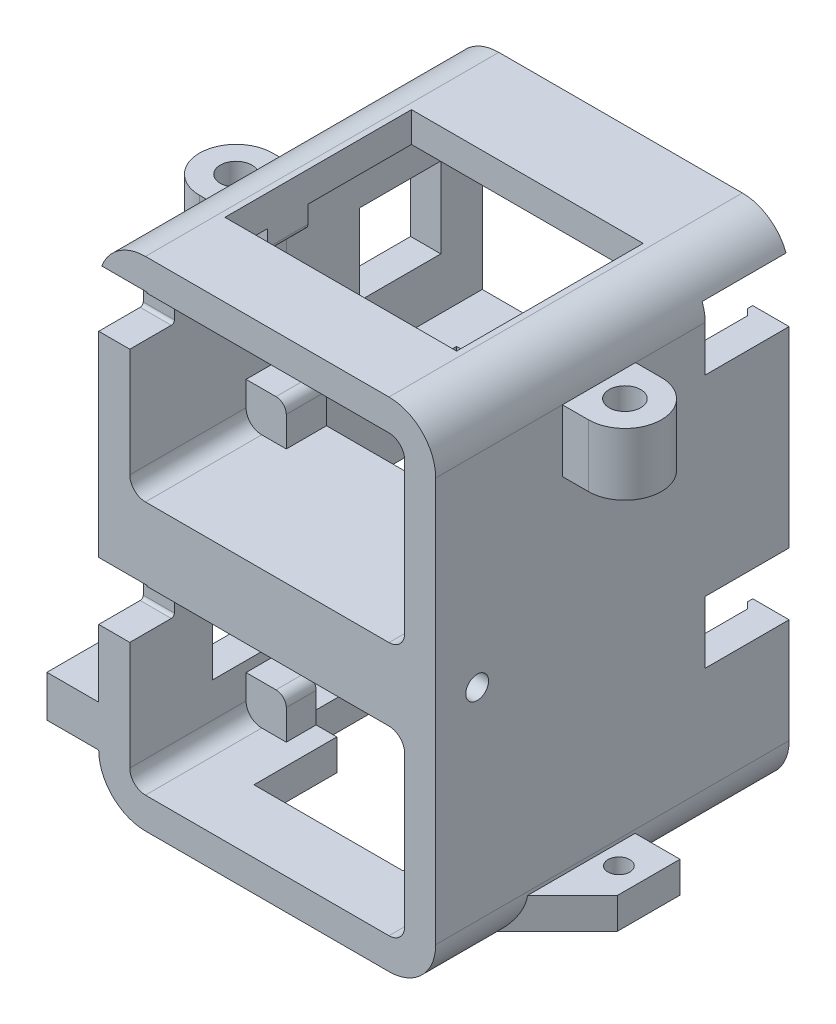
SolidWorks part; units mm, degrees
ref_plane "前视基准面" through (0, 0, 0) normal (0, 0, 1) x (1, 0, 0)
ref_plane "上视基准面" through (0, 0, 0) normal (0, 1, 0) x (1, 0, 0)
ref_plane "右视基准面" through (0, 0, 0) normal (1, 0, 0) x (0, 0, -1)
other "Configuration Table"
sketch "草图2" plane through (0, 0, 0) normal (0, 0, 1) x (1, 0, 0)
  line L20 (13.26, -7.25) -> (13.26, 7.25)
  line L21 (11.75, 8.76) -> (-16.76, 8.76)
  line L22 (-16.76, 8.76) -> (-16.76, 3.34)
  line L23 (-16.76, 3.34) -> (-13.26, 3.34)
  line L24 (-13.26, 3.34) -> (-13.26, -7.25)
  line L25 (-11.75, -8.76) -> (-3.99, -8.76)
  line L26 (-3.99, -8.76) -> (-3.99, -7.76)
  line L27 (-3.99, -7.76) -> (3.99, -7.76)
  line L28 (3.99, -7.76) -> (3.99, -8.76)
  line L29 (3.99, -8.76) -> (11.75, -8.76)
  line L40 (13.26, -7.25) -> (13.26, 7.25)
  line L41 (11.75, 8.76) -> (-16.76, 8.76)
  line L42 (-16.76, 8.76) -> (-16.76, 3.34)
  line L43 (-16.76, 3.34) -> (-13.26, 3.34)
  line L44 (-13.26, 3.34) -> (-13.26, -7.25)
  line L45 (-11.75, -8.76) -> (-3.99, -8.76)
  line L49 (3.99, -8.76) -> (11.75, -8.76)
  line L50 (-3.99, 15.74) -> (3.99, 15.74)
  line L51 (-3.99, -8.76) -> (3.99, -8.76)
  line L52 (-3.99, 12.74) -> (3.99, 12.74)
  line L53 (3.99, 12.74) -> (11.75, 12.74)
  line L54 (16.26, 17.25) -> (16.26, 31.75)
  line L55 (11.75, 36.26) -> (-19.76, 36.26)
  line L56 (-19.76, 36.26) -> (-19.76, 24.84)
  line L57 (-19.76, 24.84) -> (-16.26, 24.84)
  line L58 (-16.26, 24.84) -> (-16.26, 17.25)
  line L59 (-11.75, 12.74) -> (-3.99, 12.74)
  line L70 (13.26, 17.25) -> (13.26, 31.75)
  line L71 (11.75, 33.26) -> (-16.76, 33.26)
  line L72 (-16.76, 33.26) -> (-16.76, 27.84)
  line L73 (-16.76, 27.84) -> (-13.26, 27.84)
  line L74 (-13.26, 27.84) -> (-13.26, 17.25)
  line L75 (-11.75, 15.74) -> (-3.99, 15.74)
  line L76 (-3.99, 15.74) -> (-3.99, 16.74)
  line L77 (-3.99, 16.74) -> (3.99, 16.74)
  line L78 (3.99, 16.74) -> (3.99, 15.74)
  line L79 (3.99, 15.74) -> (11.75, 15.74)
  line L80 (13.26, 17.25) -> (13.26, 31.75)
  line L81 (11.75, 33.26) -> (-16.76, 33.26)
  line L82 (-16.76, 33.26) -> (-16.76, 27.84)
  line L83 (-16.76, 27.84) -> (-13.26, 27.84)
  line L84 (-13.26, 27.84) -> (-13.26, 17.25)
  line L85 (-11.75, 15.74) -> (-3.99, 15.74)
  line L89 (3.99, 15.74) -> (11.75, 15.74)
  line L90 (16.26, -7.25) -> (16.26, 7.25)
  line L91 (11.75, 11.76) -> (-19.76, 11.76)
  line L92 (-19.76, 11.76) -> (-19.76, 0.34)
  line L93 (-19.76, 0.34) -> (-16.26, 0.34)
  line L94 (-16.26, 0.34) -> (-16.26, -7.25)
  line L95 (-11.75, -11.76) -> (-3.99, -11.76)
  line L96 (-3.99, -11.76) -> (3.99, -11.76)
  line L97 (3.99, -11.76) -> (11.75, -11.76)
  line L98 (-16.26, 0.34) -> (-16.26, 3.34)
  line L99 (-16.26, 17.25) -> (-16.26, 11.76)
  line L100 (16.26, 17.25) -> (16.26, 7.25)
  line L101 (-16.76, 33.26) -> (-19.76, 33.26)
  line L102 (-16.76, 27.84) -> (-19.76, 27.84)
  line L103 (-16.76, 8.76) -> (-19.76, 8.76)
  line L104 (-16.26, 24.84) -> (-16.26, 27.84)
  line L105 (-16.26, 36.26) -> (-16.26, 33.26)
  line L106 (-16.26, 11.76) -> (-16.26, 8.76)
  line L107 (-16.26, 33.26) -> (-16.26, 27.84)
  line L108 (-16.26, 8.76) -> (-16.26, 3.34)
  line L109 (-13.26, 27.84) -> (-13.26, 33.26)
  line L110 (-13.26, 3.34) -> (-13.26, 8.76)
  arc A1 (-11.75, 11.76) -> (-16.26, 7.25) centre (-11.75, 7.25) ccw
  arc A2 (-11.75, 8.76) -> (-13.26, 7.25) centre (-11.75, 7.25) ccw
  arc A3 (-11.75, 8.76) -> (-13.26, 7.25) centre (-11.75, 7.25) ccw
  arc A6 (13.26, 7.25) -> (11.75, 8.76) centre (11.75, 7.25) ccw
  arc A7 (-13.26, -7.25) -> (-11.75, -8.76) centre (-11.75, -7.25) ccw
  arc A8 (11.75, -8.76) -> (13.26, -7.25) centre (11.75, -7.25) ccw
  arc A12 (13.26, 7.25) -> (11.75, 8.76) centre (11.75, 7.25) ccw
  arc A13 (-13.26, -7.25) -> (-11.75, -8.76) centre (-11.75, -7.25) ccw
  arc A14 (11.75, -8.76) -> (13.26, -7.25) centre (11.75, -7.25) ccw
  arc A15 (11.75, 12.74) -> (16.26, 17.25) centre (11.75, 17.25) ccw
  arc A16 (16.26, 31.75) -> (11.75, 36.26) centre (11.75, 31.75) ccw
  arc A17 (-16.26, 17.25) -> (-11.75, 12.74) centre (-11.75, 17.25) ccw
  arc A21 (13.26, 31.75) -> (11.75, 33.26) centre (11.75, 31.75) ccw
  arc A22 (-13.26, 17.25) -> (-11.75, 15.74) centre (-11.75, 17.25) ccw
  arc A23 (11.75, 15.74) -> (13.26, 17.25) centre (11.75, 17.25) ccw
  arc A24 (13.26, 31.75) -> (11.75, 33.26) centre (11.75, 31.75) ccw
  arc A25 (-13.26, 17.25) -> (-11.75, 15.74) centre (-11.75, 17.25) ccw
  arc A26 (11.75, 15.74) -> (13.26, 17.25) centre (11.75, 17.25) ccw
  arc A27 (16.26, 7.25) -> (11.75, 11.76) centre (11.75, 7.25) ccw
  arc A28 (-16.26, -7.25) -> (-11.75, -11.76) centre (-11.75, -7.25) ccw
  arc A29 (11.75, -11.76) -> (16.26, -7.25) centre (11.75, -7.25) ccw
  arc A31 (-11.75, 36.26) -> (-16.26, 31.75) centre (-11.75, 31.75) ccw
  arc A32 (-11.75, 33.26) -> (-13.26, 31.75) centre (-11.75, 31.75) ccw
  arc A33 (-11.75, 33.26) -> (-13.26, 31.75) centre (-11.75, 31.75) ccw
  dimension "D4" = 3
  dimension "D6" = 3
  dimension "D7" = 0.01
  dimension "D8" = 3
extrude "凸台-拉伸2" add sketch "草图2" against normal up to surface (11.22 mm away)
sketch "草图3" plane through (0, 0, -11.22) normal (0, 0, -1) x (-1, 0, 0)
  line L0 (11.75, -8.76) -> (-11.75, -8.76) construction
  line L2 (-11.75, 8.76) -> (11.75, 8.76) construction
  line L3 (11.75, -8.76) -> (-11.75, -8.76)
  line L4 (16.26, -7.25) -> (16.26, 31.75)
  line L5 (11.75, 36.26) -> (-11.75, 36.26)
  line L6 (-16.26, 31.75) -> (-16.26, -7.25)
  line L7 (-11.75, -11.76) -> (11.75, -11.76)
  line L12 (16.26, -7.25) -> (16.26, 31.75)
  line L13 (11.75, 36.26) -> (-11.75, 36.26)
  line L14 (-16.26, 31.75) -> (-16.26, -7.25)
  line L16 (-11.75, -11.76) -> (11.75, -11.76)
  line L20 (-13.26, -7.25) -> (-13.26, 7.25)
  line L21 (-11.75, 33.26) -> (11.75, 33.26) construction
  line L22 (-13.26, 17.25) -> (-13.26, 31.75) construction
  line L23 (-9.38, -8.74) -> (-9.38, -5.87)
  line L24 (-10.37, -4.88) -> (-13.24, -4.88)
  line L25 (-13.24, -4.88) -> (-13.24, -7.25)
  line L26 (-11.75, -8.74) -> (-9.38, -8.74)
  line L27 (-9.38, -8.74) -> (-9.38, -5.87)
  line L28 (-10.37, -4.88) -> (-13.24, -4.88)
  line L32 (11.75, 15.74) -> (-11.75, 15.74) construction
  line L33 (-11.75, 33.26) -> (11.75, 33.26)
  line L34 (-13.26, 17.25) -> (-13.26, 31.75)
  line L36 (11.75, 15.74) -> (-11.75, 15.74)
  line L38 (13.26, 7.25) -> (13.26, -7.25) construction
  line L39 (13.24, -4.88) -> (10.37, -4.88)
  line L40 (9.38, -5.87) -> (9.38, -8.74)
  line L41 (9.38, -8.74) -> (11.75, -8.74)
  line L42 (13.24, -7.25) -> (13.24, -4.88)
  line L43 (13.24, -4.88) -> (10.37, -4.88)
  line L44 (9.38, -5.87) -> (9.38, -8.74)
  line L47 (13.26, 7.25) -> (13.26, -7.25)
  line L48 (-11.75, 8.76) -> (11.75, 8.76) construction
  line L49 (-9.38, 15.75) -> (-9.38, 18.63)
  line L50 (-10.37, 19.62) -> (-13.25, 19.62)
  line L51 (-13.24, 6.68) -> (-11.67, 6.68)
  line L52 (-11.18, 7.17) -> (-11.18, 8.74)
  line L53 (-11.18, 8.74) -> (-11.75, 8.74)
  line L54 (-13.24, 7.25) -> (-13.24, 6.68)
  line L55 (-13.24, 6.68) -> (-11.67, 6.68)
  line L56 (-11.18, 7.17) -> (-11.18, 8.74)
  line L59 (-13.24, 6.68) -> (-13.26, 6.68)
  line L60 (-13.26, -7.25) -> (-13.26, 7.25) construction
  line L61 (-9.38, 15.74) -> (-9.38, 18.63)
  line L62 (-10.37, 19.62) -> (-13.26, 19.62)
  line L63 (11.18, 8.74) -> (11.18, 7.17)
  line L64 (11.67, 6.68) -> (13.24, 6.68)
  line L65 (13.24, 6.68) -> (13.24, 7.25)
  line L66 (11.75, 8.74) -> (11.18, 8.74)
  line L67 (11.18, 8.76) -> (11.18, 7.17)
  line L68 (11.67, 6.68) -> (13.26, 6.68)
  line L71 (-11.75, 8.76) -> (11.75, 8.76)
  line L73 (-13.25, 31.18) -> (-11.67, 31.18)
  line L74 (-11.18, 31.67) -> (-11.18, 33.25)
  line L75 (-13.25, 31.18) -> (-11.67, 31.18)
  line L76 (-11.18, 31.67) -> (-11.18, 33.25)
  line L79 (11.67, 31.18) -> (13.25, 31.18)
  line L80 (11.18, 33.25) -> (11.18, 31.67)
  line L81 (11.67, 31.18) -> (13.26, 31.18)
  line L82 (11.18, 33.25) -> (11.18, 31.67)
  line L83 (-13.25, 31.18) -> (-13.26, 31.18)
  line L84 (-11.18, 33.25) -> (-11.18, 33.26)
  line L85 (9.38, 18.63) -> (9.38, 15.75)
  line L86 (13.25, 19.62) -> (10.37, 19.62)
  line L87 (9.38, 18.63) -> (9.38, 15.74)
  line L88 (13.26, 19.62) -> (10.37, 19.62)
  line L89 (11.18, 33.25) -> (11.18, 33.26)
  line L90 (-11.18, 8.74) -> (-11.18, 8.76)
  line L91 (13.26, 31.75) -> (13.26, 17.25) construction
  line L92 (13.26, 31.75) -> (13.26, 17.25)
  line L93 (-13.24, -4.88) -> (-13.26, -4.88)
  line L94 (-9.38, -8.74) -> (-9.38, -8.76)
  line L95 (9.38, -8.74) -> (9.38, -8.76)
  line L96 (13.24, -4.88) -> (13.26, -4.88)
  arc A0 (-13.26, -7.25) -> (-11.75, -8.76) centre (-11.75, -7.25) ccw construction
  arc A1 (11.75, -8.76) -> (13.26, -7.25) centre (11.75, -7.25) ccw construction
  arc A2 (-11.75, 8.76) -> (-13.26, 7.25) centre (-11.75, 7.25) ccw construction
  arc A3 (11.75, -11.76) -> (16.26, -7.25) centre (11.75, -7.25) ccw
  arc A4 (-11.75, 36.26) -> (-16.26, 31.75) centre (-11.75, 31.75) ccw
  arc A5 (-16.26, -7.25) -> (-11.75, -11.76) centre (-11.75, -7.25) ccw
  arc A6 (11.75, -11.76) -> (16.26, -7.25) centre (11.75, -7.25) ccw
  arc A9 (-11.75, 36.26) -> (-16.26, 31.75) centre (-11.75, 31.75) ccw
  arc A10 (-9.38, -5.87) -> (-10.37, -4.88) centre (-10.37, -5.87) ccw
  arc A11 (-13.24, -7.25) -> (-11.75, -8.74) centre (-11.75, -7.25) ccw
  arc A12 (-9.38, -5.87) -> (-10.37, -4.88) centre (-10.37, -5.87) ccw
  arc A14 (-16.26, -7.25) -> (-11.75, -11.76) centre (-11.75, -7.25) ccw
  arc A15 (-13.26, -7.25) -> (-11.75, -8.76) centre (-11.75, -7.25) ccw
  arc A16 (11.75, -8.76) -> (13.26, -7.25) centre (11.75, -7.25) ccw
  arc A17 (-11.75, 8.76) -> (-13.26, 7.25) centre (-11.75, 7.25) ccw
  arc A18 (10.37, -4.88) -> (9.38, -5.87) centre (10.37, -5.87) ccw
  arc A19 (11.75, -8.74) -> (13.24, -7.25) centre (11.75, -7.25) ccw
  arc A20 (10.37, -4.88) -> (9.38, -5.87) centre (10.37, -5.87) ccw
  arc A22 (-11.75, 33.26) -> (-13.26, 31.75) centre (-11.75, 31.75) ccw construction
  arc A23 (11.75, 15.74) -> (13.26, 17.25) centre (11.75, 17.25) ccw construction
  arc A24 (-11.67, 6.68) -> (-11.18, 7.17) centre (-11.67, 7.17) ccw
  arc A25 (-11.75, 8.74) -> (-13.24, 7.25) centre (-11.75, 7.25) ccw
  arc A26 (-11.67, 6.68) -> (-11.18, 7.17) centre (-11.67, 7.17) ccw
  arc A28 (-13.26, 17.25) -> (-11.75, 15.74) centre (-11.75, 17.25) ccw construction
  arc A29 (-11.75, 33.26) -> (-13.26, 31.75) centre (-11.75, 31.75) ccw
  arc A30 (11.18, 7.17) -> (11.67, 6.68) centre (11.67, 7.17) ccw
  arc A31 (13.24, 7.25) -> (11.75, 8.74) centre (11.75, 7.25) ccw
  arc A32 (11.18, 7.17) -> (11.67, 6.68) centre (11.67, 7.17) ccw
  arc A34 (11.75, 15.74) -> (13.26, 17.25) centre (11.75, 17.25) ccw
  arc A35 (-13.26, 17.25) -> (-11.75, 15.74) centre (-11.75, 17.25) ccw
  arc A36 (13.26, 7.25) -> (11.75, 8.76) centre (11.75, 7.25) ccw construction
  arc A37 (13.26, 7.25) -> (11.75, 8.76) centre (11.75, 7.25) ccw
  arc A38 (-9.38, 18.63) -> (-10.37, 19.62) centre (-10.37, 18.63) ccw
  arc A39 (-9.38, 18.63) -> (-10.37, 19.62) centre (-10.37, 18.63) ccw
  arc A41 (-11.67, 31.18) -> (-11.18, 31.67) centre (-11.67, 31.67) ccw
  arc A42 (-11.67, 31.18) -> (-11.18, 31.67) centre (-11.67, 31.67) ccw
  arc A44 (11.18, 31.67) -> (11.67, 31.18) centre (11.67, 31.67) ccw
  arc A45 (11.18, 31.67) -> (11.67, 31.18) centre (11.67, 31.67) ccw
  arc A46 (13.26, 31.75) -> (11.75, 33.26) centre (11.75, 31.75) ccw construction
  arc A47 (10.37, 19.62) -> (9.38, 18.63) centre (10.37, 18.63) ccw
  arc A48 (10.37, 19.62) -> (9.38, 18.63) centre (10.37, 18.63) ccw
  arc A49 (13.26, 31.75) -> (11.75, 33.26) centre (11.75, 31.75) ccw
  arc A52 (16.26, 31.75) -> (11.75, 36.26) centre (11.75, 31.75) ccw
  arc A53 (16.26, 31.75) -> (11.75, 36.26) centre (11.75, 31.75) ccw
  dimension "D7" = 0.01
  dimension "D9" = 0.01
extrude "凸台-拉伸3" add sketch "草图3" along normal up to surface (3.88 mm away)
sketch "草图4" plane through (-16.26, 0, 0) normal (-1, 0, 0) x (0, 0, 1)
  line L8 (0.1, 8.85) -> (-4, 8.85)
  line L9 (-4.3, 8.55) -> (-4.3, 3.55)
  line L10 (-4, 3.25) -> (0.1, 3.25)
  line L11 (0.1, 3.25) -> (0.1, 8.85)
  line L12 (0.1, 8.85) -> (-4, 8.85)
  line L13 (-4.3, 8.55) -> (-4.3, 3.55)
  line L14 (-4, 3.25) -> (0.1, 3.25)
  line L15 (0.1, 3.25) -> (0.1, 8.85)
  line L20 (0.1, 33.35) -> (-4, 33.35)
  line L21 (-4.3, 33.05) -> (-4.3, 28.05)
  line L22 (-4, 27.75) -> (0.1, 27.75)
  line L23 (0.1, 27.75) -> (0.1, 33.35)
  line L24 (0.1, 33.35) -> (-4, 33.35)
  line L25 (-4.3, 33.05) -> (-4.3, 28.05)
  line L26 (-4, 27.75) -> (0.1, 27.75)
  line L27 (0.1, 27.75) -> (0.1, 33.35)
  arc A4 (-4, 8.85) -> (-4.3, 8.55) centre (-4, 8.55) ccw
  arc A5 (-4.3, 3.55) -> (-4, 3.25) centre (-4, 3.55) ccw
  arc A6 (-4, 8.85) -> (-4.3, 8.55) centre (-4, 8.55) ccw
  arc A7 (-4.3, 3.55) -> (-4, 3.25) centre (-4, 3.55) ccw
  arc A10 (-4, 33.35) -> (-4.3, 33.05) centre (-4, 33.05) ccw
  arc A11 (-4.3, 28.05) -> (-4, 27.75) centre (-4, 28.05) ccw
  arc A12 (-4, 33.35) -> (-4.3, 33.05) centre (-4, 33.05) ccw
  arc A13 (-4.3, 28.05) -> (-4, 27.75) centre (-4, 28.05) ccw
extrude "切除-拉伸1" cut sketch "草图4" against normal blind 4.65
ref_plane "基准面1" through (0, 31.75, 0) normal (0, 1, 0) x (1, 0, 0)
sketch "草图8" plane through (0, 31.75, 0) normal (0, 1, 0) x (1, 0, 0)
  line L0 (18.76, 12.23) -> (15.235, 12.23)
  line L1 (15.235, 12.23) -> (15.235, 15.755)
  line L2 (16.26, 15.1) -> (16.26, 0) construction
  line L3 (-12.113, 15.755) -> (15.235, 15.755) construction
  line L4 (9.73, 15.91) -> (-9.73, 15.91) construction
  line L5 (-9.73, 15.6) -> (9.73, 15.6) construction
  line L9 (18.76, 19.28) -> (15.235, 19.28)
  line L10 (15.235, 15.755) -> (15.235, 19.28)
  circle A2 centre (18.76, 15.755) radius 1.525
  circle A3 centre (18.76, 15.755) radius 3.525
  dimension "D1" = 3.05
  dimension "D3" = 2.5
  dimension "D2" = 2
extrude "凸台-拉伸5" add sketch "草图8" against normal blind 6 contours A3 A2 | A3 L9 L10 | A3 L1 L0
mirror "镜向1" about plane through (0, 0, 0) normal (1, 0, 0) of "凸台-拉伸5"
sketch "草图9" plane through (0, 0, -15.1) normal (0, 0, -1) x (-1, 0, 0)
  line L0 (-11.18, 33.26) -> (11.18, 33.26) construction
  line L1 (-11.18, 33.26) -> (11.18, 33.26)
  line L2 (-11.18, 33.26) -> (-11.18, 36.26)
  line L3 (-11.18, 36.26) -> (11.18, 36.26)
  line L4 (11.18, 33.26) -> (11.18, 36.26)
  line L5 (11.75, 36.26) -> (-11.75, 36.26) construction
  line L6 (-11.18, 31.67) -> (-11.18, 33.26) construction
  line L7 (11.18, 33.26) -> (11.18, 31.67) construction
extrude "切除-拉伸3" cut sketch "草图9" against normal blind 8
sketch "草图10" plane through (0, 0, -15.1) normal (0, 0, -1) x (-1, 0, 0)
  line L0 (-11.75, -11.76) -> (11.75, -11.76) construction
  line L1 (-10.73, -11.76) -> (10.73, -11.76)
  line L2 (-10.73, -11.76) -> (-10.73, -4.88)
  line L3 (-10.73, -4.88) -> (10.73, -4.88)
  line L4 (10.73, -11.76) -> (10.73, -4.88)
  line L5 (13.26, -4.88) -> (10.37, -4.88) construction
  line L6 (-9.73, 21.7989) -> (-9.73, 20.8989) construction
  line L7 (9.73, 69.5489) -> (9.73, -48.1511) construction
  dimension "D1" = 1
  dimension "D2" = 1
extrude "切除-拉伸4" cut sketch "草图10" against normal blind 1
sketch "草图12" plane through (-16.26, 0, 0) normal (-1, 0, 0) x (0, 0, 1)
  line L0 (0, 8.85) -> (0, 27.75) construction
  line L1 (-11.22, 8.76) -> (-4.2142, 8.76) construction
  line L2 (-11.22, 15.74) -> (0, 15.74) construction
  line L3 (-11.22, 8.76) -> (-4.2142, 8.76)
  line L4 (-11.22, 15.74) -> (0, 15.74)
  line L5 (-8.8508, 12.25) -> (0.722, 12.25) construction
  circle A0 centre (-4, 12.25) radius 1.1
  dimension "D1" = 2.2
  dimension "D2" = 4
extrude "切除-拉伸5" cut sketch "草图12" against normal blind 8 contours A0 L5 | L5 A0
mirror "镜向2" about plane through (0, 0, 0) normal (1, 0, 0) of "切除-拉伸5"
sketch "草图14" plane through (0, 0, -15.1) normal (0, 0, -1) x (-1, 0, 0)
  line L0 (-16.26, 19.53) -> (16.26, 19.53)
  line L2 (-16.26, 8.85) -> (16.26, 8.85)
  line L3 (-10.37, 19.63) -> (-13.25, 19.63) construction
  line L13 (-11.17, 8.75) -> (11.17, 8.75) construction
  line L19 (16.26, 3.25) -> (13.26, 3.25)
  line L20 (16.26, -7.25) -> (16.26, 3.25)
  line L21 (-11.75, -11.76) -> (11.75, -11.76)
  line L22 (-16.26, 31.75) -> (-16.26, -7.25)
  line L23 (11.75, 36.26) -> (-11.75, 36.26)
  line L24 (11.61, 33.35) -> (15.9666, 33.35)
  line L26 (-11.75, 33.26) -> (11.61, 33.26)
  line L27 (-13.26, 17.25) -> (-13.26, 31.75)
  line L28 (11.75, 15.74) -> (-11.75, 15.74)
  line L29 (13.26, 27.75) -> (13.26, 17.25)
  line L30 (16.26, 27.75) -> (13.26, 27.75)
  line L31 (16.26, 8.85) -> (16.26, 27.75)
  line L32 (11.61, 8.85) -> (16.26, 8.85)
  line L34 (-11.75, 8.76) -> (11.61, 8.76)
  line L35 (-13.26, -7.25) -> (-13.26, 7.25)
  line L36 (11.75, -8.76) -> (-11.75, -8.76)
  line L37 (13.26, 3.25) -> (13.26, -7.25)
  line L39 (16.26, -7.25) -> (16.26, 8.85)
  line L40 (-11.75, -11.76) -> (11.75, -11.76)
  line L41 (-16.26, 31.75) -> (-16.26, -7.25)
  line L42 (11.75, 36.26) -> (-11.75, 36.26)
  line L50 (16.26, 8.85) -> (16.26, 31.75)
  line L66 (11.61, 33.26) -> (11.61, 33.35)
  line L67 (11.61, 8.76) -> (11.61, 8.85)
  line L1654 (-9.83, 69.5959) -> (-9.83, -48.2511)
  line L1655 (-9.83, -48.2511) -> (9.83, -48.2511)
  line L1656 (9.83, -48.2511) -> (9.83, 69.5959)
  line L1657 (-9.83, 69.5959) -> (-9.83, -48.2511)
  line L1658 (-9.83, -48.2511) -> (9.83, -48.2511)
  line L1659 (9.83, -48.2511) -> (9.83, 69.5959)
  arc A4 (9.83, 69.5959) -> (-9.83, 69.5959) centre (0, 57.7742) ccw
  arc A5 (9.83, 69.5959) -> (-9.83, 69.5959) centre (0, 57.7742) ccw
  arc A10 (11.75, -11.76) -> (16.26, -7.25) centre (11.75, -7.25) ccw
  arc A11 (-16.26, -7.25) -> (-11.75, -11.76) centre (-11.75, -7.25) ccw
  arc A12 (-11.75, 36.26) -> (-16.26, 31.75) centre (-11.75, 31.75) ccw
  arc A13 (15.9666, 33.35) -> (11.75, 36.26) centre (11.75, 31.75) ccw
  arc A14 (-11.75, 33.26) -> (-13.26, 31.75) centre (-11.75, 31.75) ccw
  arc A15 (-13.26, 17.25) -> (-11.75, 15.74) centre (-11.75, 17.25) ccw
  arc A16 (11.75, 15.74) -> (13.26, 17.25) centre (11.75, 17.25) ccw
  arc A17 (-11.75, 8.76) -> (-13.26, 7.25) centre (-11.75, 7.25) ccw
  arc A18 (-13.26, -7.25) -> (-11.75, -8.76) centre (-11.75, -7.25) ccw
  arc A19 (11.75, -8.76) -> (13.26, -7.25) centre (11.75, -7.25) ccw
  arc A20 (11.75, -11.76) -> (16.26, -7.25) centre (11.75, -7.25) ccw
  arc A21 (-16.26, -7.25) -> (-11.75, -11.76) centre (-11.75, -7.25) ccw
  arc A22 (-11.75, 36.26) -> (-16.26, 31.75) centre (-11.75, 31.75) ccw
  arc A23 (16.26, 31.75) -> (11.75, 36.26) centre (11.75, 31.75) ccw
  dimension "D3" = 0.1
  dimension "D4" = 0.1
extrude "凸台-拉伸7" add sketch "草图14" along normal blind 3
sketch "草图15" plane through (0, 0, -15.1) normal (0, 0, -1) x (-1, 0, 0)
  line L0 (-16.26, 25.75) -> (-16.26, 19.53) construction
  line L7 (-16.26, 19.53) -> (-16.26, 8.85) construction
  line L8 (-16.26, 8.85) -> (-16.26, -7.25) construction
  line L10 (-10.73, -11.76) -> (10.73, -11.76) construction
  line L22 (16.26, -7.25) -> (16.26, 8.85) construction
  line L23 (16.26, 8.85) -> (16.26, 19.53) construction
  line L32 (16.26, 19.53) -> (16.26, 25.75) construction
  line L37 (11.18, 36.26) -> (-11.18, 36.26) construction
  line L38 (-16.26, 31.75) -> (-16.26, 19.53)
  line L39 (-16.26, 19.53) -> (-16.26, 8.85)
  line L42 (-16.26, 8.85) -> (-16.26, -7.25)
  line L43 (-11.75, -11.76) -> (11.75, -11.76)
  line L44 (16.26, -7.25) -> (16.26, 8.85)
  line L45 (16.26, 8.85) -> (16.26, 19.53)
  line L46 (16.26, 19.53) -> (16.26, 31.75)
  line L47 (11.75, 36.26) -> (-11.75, 36.26)
  line L48 (-11.17, 33.25) -> (11.17, 33.25) construction
  line L49 (-13.35, 33.35) -> (13.35, 33.35)
  line L54 (-13.35, 33.35) -> (-13.35, -8.85)
  line L55 (-13.35, -8.85) -> (13.35, -8.85)
  line L56 (13.35, 33.35) -> (13.35, -8.85)
  line L58 (13.25, 6.67) -> (13.25, -4.87) construction
  line L59 (9.37, -8.75) -> (-9.37, -8.75) construction
  line L60 (-13.25, -4.87) -> (-13.25, 6.67) construction
  arc A8 (-16.26, -7.25) -> (-11.75, -11.76) centre (-11.75, -7.25) ccw construction
  arc A9 (11.75, -11.76) -> (16.26, -7.25) centre (11.75, -7.25) ccw construction
  arc A10 (16.26, 31.75) -> (11.75, 36.26) centre (11.75, 31.75) ccw construction
  arc A11 (-11.75, 36.26) -> (-16.26, 31.75) centre (-11.75, 31.75) ccw construction
  arc A12 (-16.26, -7.25) -> (-11.75, -11.76) centre (-11.75, -7.25) ccw
  arc A13 (11.75, -11.76) -> (16.26, -7.25) centre (11.75, -7.25) ccw
  arc A14 (16.26, 31.75) -> (11.75, 36.26) centre (11.75, 31.75) ccw
  arc A15 (-11.75, 36.26) -> (-16.26, 31.75) centre (-11.75, 31.75) ccw
  dimension "D2" = 0.1
  dimension "D1" = 0.1
  dimension "D3" = 0.1
  dimension "D4" = 0.1
extrude "凸台-上半部分" add sketch "草图15" along normal blind 19
sketch "草图16" plane through (0, 0, -18.1) normal (0, 0, -1) x (-1, 0, 0)
  line L1 (-13.35, 8.85) -> (13.35, 8.85)
  line L2 (-13.35, 8.85) -> (-13.35, 15.65)
  line L3 (-13.35, 15.65) -> (13.35, 15.65)
  line L4 (13.35, 8.85) -> (13.35, 15.65)
  line L12 (-13.35, 33.35) -> (-13.35, -8.85) construction
  line L13 (13.35, 33.35) -> (13.35, -8.85) construction
  line L15 (-4, 15.75) -> (-11.75, 15.75) construction
  line L16 (-11.17, 8.75) -> (11.17, 8.75) construction
  dimension "D2" = 0.1
  dimension "D1" = 0.1
extrude "凸台-拉伸9" add sketch "草图16" along normal up to surface (16 mm away) up to face at (0, 12.25, -34.1)
sketch "草图17" plane through (0, 8.85, 0) normal (0, -1, 0) x (1, 0, 0)
  line L2 (11.75, -34.1) -> (-11.75, -34.1) construction
  line L3 (-9.83, -18.1) -> (9.83, -18.1)
  line L5 (-9.83, -18.1) -> (9.83, -18.1)
  line L6 (-9.83, -18.1) -> (-9.83, -28.1)
  line L7 (-9.83, -28.1) -> (9.83, -28.1)
  line L8 (9.83, -18.1) -> (9.83, -28.1)
  line L10 (9.83, -18.1) -> (-9.83, -18.1) construction
  line L11 (9.83, -18.1) -> (9.83, -15.1) construction
  line L13 (9.83, -18.1) -> (-9.83, -18.1) construction
  point P1 (9.9785, -18.1)
  point P2 (-9.7893, -18.1)
  point P4 (9.83, -18.1)
  point P10 (-9.83, -18.1)
  dimension "D1" = 6
extrude "切除-拉伸8" cut sketch "草图17" against normal up to next contours L8 L3 L6 L7
sketch "草图18" plane through (13.35, 0, 0) normal (-1, 0, 0) x (0, 0, 1)
  line L0 (0, -7.25) -> (0, 31.75) construction
  line L1 (-34.1, 2.85) -> (-26, 2.85)
  line L2 (-34.1, 2.85) -> (-34.1, 8.85)
  line L3 (-34.1, 8.85) -> (-26, 8.85)
  line L4 (-26, 2.85) -> (-26, 8.85)
  line L5 (-34.1, 27.35) -> (-26, 27.35)
  line L6 (-34.1, 27.35) -> (-34.1, 33.35)
  line L7 (-34.1, 33.35) -> (-26, 33.35)
  line L8 (-26, 27.35) -> (-26, 33.35)
  line L9 (-34.1, -7.25) -> (-34.1, 31.75) construction
  line L10 (-34.1, 8.85) -> (-34.1, -8.85) construction
  line L11 (-34.1, 8.85) -> (-15.1, 8.85) construction
  dimension "D2" = 6
  dimension "D3" = 6
  dimension "D5" = 26
extrude "切除-拉伸9" cut sketch "草图18" against normal up to next
sketch "草图19" plane through (0, -11.76, 0) normal (0, -1, 0) x (1, 0, 0)
  line L1 (-10.73, -14.1) -> (10.73, -14.1)
  line L2 (-10.73, -14.1) -> (-10.73, -15.1)
  line L3 (-10.73, -15.1) -> (10.73, -15.1)
  line L4 (10.73, -14.1) -> (10.73, -15.1)
  line L5 (-10.73, -15.1) -> (10.73, -15.1)
  line L6 (-10.73, -15.1) -> (-10.73, -25.1)
  line L7 (-10.73, -25.1) -> (10.73, -25.1)
  line L8 (10.73, -15.1) -> (10.73, -25.1)
  dimension "D1" = 10
extrude "切除-拉伸10" cut sketch "草图19" against normal up to next
sketch "草图24" plane through (0, -11.76, 0) normal (0, -1, 0) x (1, 0, 0)
  line L0 (9.38, -14.1) -> (-9.38, -14.1) construction
  line L1 (9.38, -14.1) -> (-9.38, -14.1)
  line L3 (-7, -6.1) -> (7, -6.1)
  line L4 (-7, -6.1) -> (-7, -14.1)
  line L5 (-7, -14.1) -> (7, -14.1)
  line L6 (7, -6.1) -> (7, -14.1)
  line L7 (-7, -6.1) -> (7, -14.1) construction
  line L8 (-7, -14.1) -> (7, -6.1) construction
  point P2 (0, -10.1)
  dimension "D1" = 8
  dimension "D2" = 14
extrude "切除-拉伸14" cut sketch "草图24" against normal up to next contours L6 L3 L4 L1
sketch "草图20" plane through (0, 36.26, 0) normal (0, 1, 0) x (1, 0, 0)
  line L1 (-11.18, 15.1) -> (11.18, 15.1)
  line L2 (-11.18, 15.1) -> (-11.18, 25.1)
  line L3 (-11.18, 25.1) -> (11.18, 25.1)
  line L4 (11.18, 15.1) -> (11.18, 25.1)
  dimension "D1" = 10
extrude "切除-拉伸11" cut sketch "草图20" against normal up to next
sketch "草图21" plane through (13.35, 0, 0) normal (-1, 0, 0) x (0, 0, 1)
  line L0 (-34.1, 27.35) -> (-34.1, 15.65) construction
  line L5 (-34.1, 2.85) -> (-26, 2.85) construction
  line L6 (-34.1, 27.35) -> (-32.6, 27.35)
  line L7 (-34.1, 27.35) -> (-34.1, 22.35)
  line L8 (-34.1, 22.35) -> (-32.6, 22.35)
  line L9 (-32.6, 27.35) -> (-32.6, 22.35)
  line L10 (-34.1, 2.85) -> (-32.6, 2.85)
  line L11 (-34.1, 2.85) -> (-34.1, -2.15)
  line L12 (-34.1, -2.15) -> (-32.6, -2.15)
  line L13 (-32.6, 2.85) -> (-32.6, -2.15)
  dimension "D1" = 5
  dimension "D2" = 1.5
extrude "凸台-拉伸10" add sketch "草图21" along normal blind 0.6
chamfer "倒角1" distance 1 angle 45 2 edges at (12.75, 0.35, -32.6) (12.75, 24.85, -32.6)
sketch "草图22" plane through (-16.26, 0, 0) normal (-1, 0, 0) x (0, 0, 1)
  line L0 (-15.1, 6.68) -> (-15.1, -4.88) construction
  line L1 (-15.1, 6.68) -> (-15.1, -4.88)
  line L2 (-44.3237, 0.9) -> (-2.0599, 0.9) construction
  line L3 (-34.1, 15.65) -> (-18.1, 15.65) construction
  line L4 (-30.1, 5.68) -> (-8, 5.68)
  line L5 (-30.1, 5.68) -> (-30.1, -3.88)
  line L6 (-30.1, -3.88) -> (-8, -3.88)
  line L7 (-8, 5.68) -> (-8, -3.88)
  line L8 (-30.1, 5.68) -> (-8, -3.88) construction
  line L9 (-30.1, -3.88) -> (-8, 5.68) construction
  line L10 (0, -7.25) -> (0, 3.25) construction
  line L11 (-45.0764, 24.5) -> (-5.8743, 24.5) construction
  line L12 (-15.1, 31.18) -> (-15.1, 19.62) construction
  line L13 (-30.1, 28.38) -> (-22.2401, 28.38)
  line L14 (-30.1, 28.38) -> (-30.1, 20.62)
  line L15 (-30.1, 20.62) -> (-22.2401, 20.62)
  line L16 (-22.2401, 28.38) -> (-22.2401, 20.62)
  line L17 (-34.1, 33.35) -> (-15.1, 33.35) construction
  line L23 (-34.1, 15.65) -> (-18.1, 15.65)
  line L24 (-34.1, 33.35) -> (-34.1, 15.65)
  line L25 (-15.1, 33.35) -> (-34.1, 33.35)
  line L26 (-15.1, 18.68) -> (-15.1, 33.35)
  line L27 (-18.1, 18.68) -> (-15.1, 18.68)
  line L28 (-18.1, 15.65) -> (-18.1, 18.68)
  line L29 (-30.1, 28.38) -> (-22.2401, 20.62) construction
  line L30 (-30.1, 20.62) -> (-22.2401, 28.38) construction
  line L31 (-15.1, 31.18) -> (-15.1, 19.62)
  line L32 (-18.2401, 25.75) -> (-18.2401, 31.75) construction
  line L33 (-18.2401, 25.75) -> (-18.2401, 31.75)
  line L35 (-34.1, -7.25) -> (-34.1, 31.75) construction
  point P2 (-15.1, 0.9)
  point P5 (-19.05, 0.9)
  point P20 (-26.17, 24.5)
  dimension "D1" = 4
  dimension "D2" = 8
  dimension "D3" = 1
  dimension "D5" = 1
  dimension "D6" = 4
extrude "切除-拉伸12" cut sketch "草图22" against normal up to next contours L5 L6 L1 L4 | L7 L4 L1 L6 | L16 L13 L14 L15
sketch "草图23" plane through (0, -11.76, 0) normal (0, -1, 0) x (1, 0, 0)
  line L0 (10.73, -14.1) -> (7, -14.1) construction
  line L1 (-7.38, -6.1) -> (7.38, -6.1)
  line L2 (-7.38, -6.1) -> (-7.38, -14.1)
  line L3 (-7.38, -14.1) -> (7.38, -14.1)
  line L4 (7.38, -6.1) -> (7.38, -14.1)
  line L5 (-7.38, -6.1) -> (7.38, -14.1) construction
  line L6 (-7.38, -14.1) -> (7.38, -6.1) construction
  line L8 (9.38, -14.1) -> (9.38, -11.22)
  line L9 (7, -14.1) -> (9.38, -14.1)
  line L10 (-9.38, -11.22) -> (-9.38, -14.1)
  line L11 (-11.75, -11.22) -> (-9.38, -11.22)
  line L12 (-11.75, 0) -> (-11.75, -11.22)
  line L13 (11.75, 0) -> (-11.75, 0)
  line L14 (11.75, -11.22) -> (11.75, 0)
  line L15 (9.38, -11.22) -> (11.75, -11.22)
  line L16 (9.38, -14.1) -> (9.38, -11.22)
  line L17 (7, -14.1) -> (9.38, -14.1)
  line L18 (-9.38, -11.22) -> (-9.38, -14.1)
  line L19 (-11.75, -11.22) -> (-9.38, -11.22)
  line L20 (-11.75, 0) -> (-11.75, -11.22)
  line L21 (11.75, 0) -> (-11.75, 0)
  line L22 (11.75, -11.22) -> (11.75, 0)
  line L23 (9.38, -11.22) -> (11.75, -11.22)
  line L35 (7, -6.1) -> (7, -14.1)
  line L36 (7, -6.1) -> (7, -14.1)
  line L37 (-7, -6.1) -> (7, -6.1)
  line L38 (-7, -6.1) -> (7, -6.1)
  line L39 (-7, -14.1) -> (-7, -6.1)
  line L40 (-7, -14.1) -> (-7, -6.1)
  line L41 (-9.38, -14.1) -> (-7, -14.1)
  line L42 (-9.38, -14.1) -> (-7, -14.1)
  point P2 (0, -10.1)
  line M19 (-10.73, -14.1) -> (-7, -14.1)
  dimension "D2" = 2
  dimension "D3" = 8
  dimension "D1" = 0
extrude "切除-拉伸13" cut sketch "草图23" against normal up to next contours L4 L1 L2 M19
ref_plane "基准面2" through (0, -10.58, 0) normal (0, 1, 0) x (1, 0, 0)
sketch "草图25" plane through (0, -10.58, 0) normal (0, 1, 0) x (1, 0, 0)
  line L2 (14.58, 19.255) -> (14.58, 7.2053)
  line L3 (20.58, 9.855) -> (20.58, 21.655) construction
  line L4 (20.58, 13.2053) -> (14.58, 7.2053)
  line L6 (20.58, 13.2053) -> (20.58, 19.255)
  line L8 (14.58, 19.255) -> (20.58, 19.255)
  arc A0 (17.4201, 15.105) -> (17.4201, 16.405) centre (18.18, 15.755) ccw construction
  circle A2 centre (18.18, 15.755) radius 1.05
  dimension "D2" = 2.1
  dimension "D1" = 45
  dimension "D4" = 6
  dimension "D3" = 3.5
  dimension "D5" = 3.5
extrude "凸台-舵机固定耳" add sketch "草图25" along normal blind 3
sketch "草图26" plane through (0, 0, 0) normal (0, 0, 1) x (1, 0, 0)
  line L1 (-16.26, -7.25) -> (-21.26, -7.25)
  line L2 (-16.26, -7.25) -> (-16.26, -3.25)
  line L3 (-16.26, -3.25) -> (-21.26, -3.25)
  line L4 (-21.26, -7.25) -> (-21.26, -3.25)
  line L5 (-16.26, -7.25) -> (-16.26, -3.25)
  line L6 (-16.26, -7.25) -> (-16.26, 3.25) construction
  arc A0 (-16.26, -7.25) -> (-11.75, -11.76) centre (-11.75, -7.25) ccw construction
  arc A1 (-16.26, -7.25) -> (-11.75, -11.76) centre (-11.75, -7.25) ccw
  line M6 (-16.26, 3.25) -> (-16.26, -7.25)
  arc M7 (-16.26, -7.25) -> (-11.75, -11.76) centre (-11.75, -7.25) ccw
  dimension "D1" = 4
  dimension "D2" = 5
extrude "凸台-拉伸12" add sketch "草图26" against normal blind 7 contours L4 L1 L3 M7 M6
sketch "草图27" plane through (0, -3.25, 0) normal (0, 1, 0) x (1, 0, 0)
  line L0 (-22.829, 3.5) -> (-15.5832, 3.5) construction
  line L3 (-16.26, 7) -> (-16.26, 0) construction
  line L5 (-21.26, 7) -> (-21.26, 0) construction
  circle A0 centre (-17.76, 3.5) radius 1.05
  point P10 (-21.26, 3.5)
  dimension "D2" = 2.1
  dimension "D1" = 1.5
extrude "切除-拉伸15" cut sketch "草图27" against normal through all
equation "\"top_residual_len\"= 0.1"
equation "\"interval_tight\"= 0.01"
equation "\"D5@草图2\"=\"interval_tight\""
equation "\"D2@草图2\"=\"interval_tight\""
equation "\"D7@草图2\"=\"interval_tight\""
equation "\"D1@草图2\"=\"interval_tight\""
equation "\"D7@草图3\"=\"interval_tight\""
equation "\"D8@草图3\"=\"interval_tight\""
equation "\"D9@草图3\"=\"interval_tight\""
equation "\"D6@草图3\"=\"interval_tight\""
equation "\"D3@草图3\"=\"interval_tight\""
equation "\"interval_loose\"= 0.1"
equation "\"D1@草图4\"=\"interval_loose\""
equation "\"D2@草图4\"=\"interval_loose\""
equation "\"D1@草图3\"=\"interval_tight\""
equation "\"D2@草图3\"=\"interval_tight\""
equation "\"D4@草图3\"=\"interval_tight\""
equation "\"D1@草图15\"=\"top_residual_len\""
equation "\"D2@草图15\"=\"top_residual_len\""
equation "\"D3@草图15\"=\"top_residual_len\""
equation "\"D4@草图15\"=\"top_residual_len\""
equation "\"D2@草图16\"=\"top_residual_len\""
equation "\"D3@草图14\"=\"top_residual_len\""
equation "\"D1@草图16\"=\"top_residual_len\""
equation "\"D4@草图14\"=\"top_residual_len\""
equation "\"M2.5_pilot_hole\"= 2.1"
equation "\"D2@草图27\"=\"M2.5_pilot_hole\""
equation "\"M2.5_clear_hole\"= 2.6"
equation "\"D2@草图25\"=\"M2.5_pilot_hole\""
equation "\"D2@草图14\"=\"top_residual_len\""
